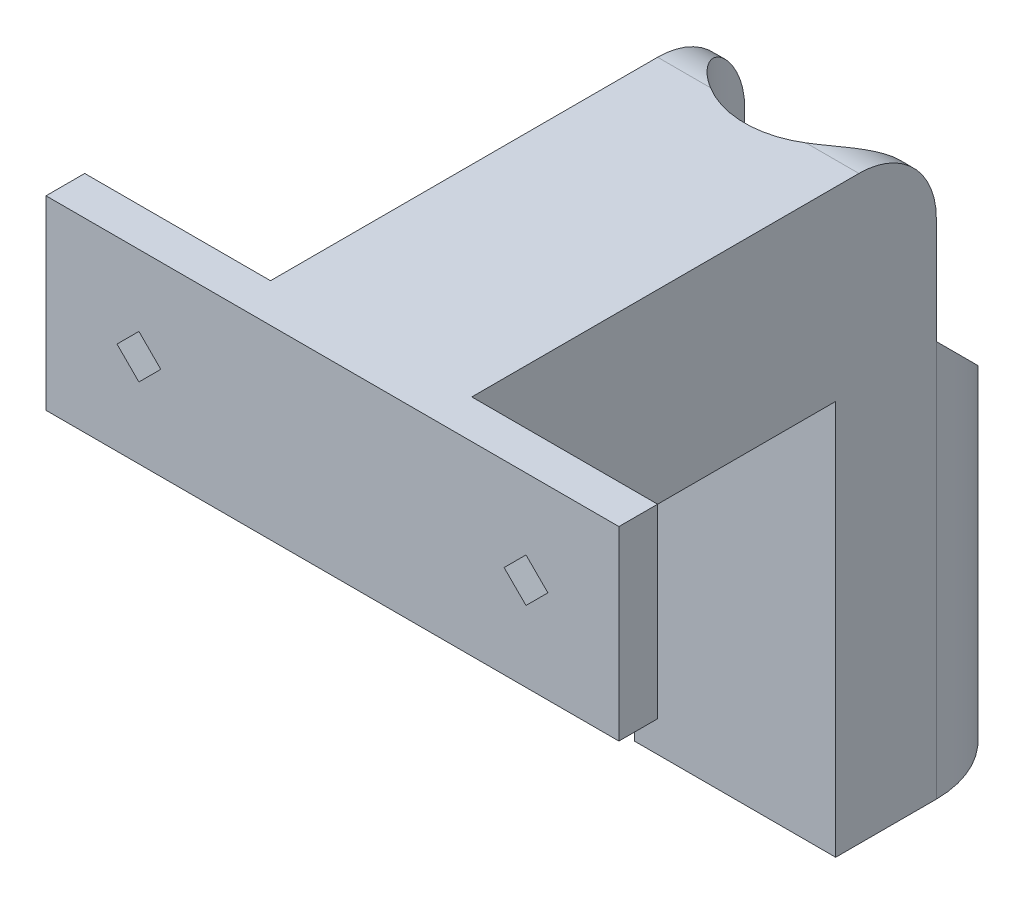
SolidWorks part; units mm, degrees
ref_plane "Front Plane" through (0, 0, 0) normal (0, 0, 1) x (1, 0, 0)
ref_plane "Top Plane" through (0, 0, 0) normal (0, 1, 0) x (1, 0, 0)
ref_plane "Right Plane" through (0, 0, 0) normal (1, 0, 0) x (0, 0, -1)
sketch "Sketch1" plane through (0, 0, 0) normal (0, 1, 0) x (1, 0, 0)
  circle A0 centre (0, 0) radius 11.25
  circle A1 centre (0, 0) radius 13
  dimension "D1" = 22.5
  dimension "D2" = 26
extrude "Boss-Extrude1" add sketch "Sketch1" along normal blind 1.2
sketch "Sketch2" plane through (0, 1.2, 0) normal (0, 1, 0) x (1, 0, 0)
  circle A0 centre (0, 0) radius 11.75
  circle A1 centre (0, 0) radius 13
  circle A2 centre (0, 0) radius 13 construction
  dimension "D1" = 23.5
extrude "Boss-Extrude2" add sketch "Sketch2" along normal blind 50
chamfer "Chamfer1" distance 0.5 angle 45 1 edges at (0, 1.2, 11.25)
sketch "Sketch3" plane through (0, 0, 0) normal (0, -1, 0) x (1, 0, 0)
  line L0 (-13, 0) -> (-13, 13)
  line L1 (-13, 13) -> (0, 13)
  line L2 (0, 13) -> (13, 13)
  line L3 (13, 13) -> (13, 0)
  line L4 (13, 0) -> (11.75, 0)
  line L5 (-13, 0) -> (-11.75, 0)
  circle A0 centre (0, 0) radius 13 construction
  circle A1 centre (0, 0) radius 11.75 construction
  arc A2 (11.75, 0) -> (-11.75, 0) centre (0, 0) ccw
  circle A3 centre (0, 0) radius 11.75 construction
  circle A4 centre (0, 0) radius 13 construction
extrude "Boss-Extrude3" add sketch "Sketch3" against normal blind 75
sketch "Sketch4" plane through (13, 0, 0) normal (1, 0, 0) x (0, 0, -1)
  line L1 (-13, 75) -> (-65, 75)
  line L2 (-13, 75) -> (-13, 51)
  line L3 (-13, 51) -> (-65, 51)
  line L4 (-65, 75) -> (-65, 51)
  dimension "D1" = 52
  dimension "D2" = 24
extrude "Boss-Extrude4" add sketch "Sketch4" against normal up to surface (26 mm away) up to face at (-13, 40.24, 5.2)
sketch "Sketch5" plane through (0, 0, 65) normal (0, 0, 1) x (1, 0, 0)
  line L0 (-13, 75) -> (-13, 51) construction
  line L1 (-13, 75) -> (-37, 75)
  line L2 (-13, 75) -> (-13, 51)
  line L3 (-13, 51) -> (-37, 51)
  line L4 (-37, 75) -> (-37, 51)
  line L5 (13, 51) -> (37, 51)
  line L6 (13, 51) -> (13, 75)
  line L7 (13, 75) -> (37, 75)
  line L8 (37, 51) -> (37, 75)
  line L9 (-13, 75) -> (13, 75) construction
  line L10 (-37, 75) -> (-13, 51) construction
  line L11 (-13, 75) -> (-37, 51) construction
  line L12 (13, 75) -> (37, 51) construction
  line L13 (37, 75) -> (13, 51) construction
  line L14 (-27.8284, 63) -> (-25, 65.8284)
  line L15 (-27.8284, 63) -> (-25, 60.1716)
  line L16 (-25, 65.8284) -> (-22.1716, 63)
  line L17 (-25, 60.1716) -> (-22.1716, 63)
  line L18 (-27.8284, 63) -> (-22.1716, 63) construction
  line L19 (-25, 65.8284) -> (-25, 60.1716) construction
  line L20 (22.1716, 63) -> (25, 65.8284)
  line L21 (22.1716, 63) -> (25, 60.1716)
  line L22 (25, 65.8284) -> (27.8284, 63)
  line L23 (25, 60.1716) -> (27.8284, 63)
  line L24 (22.1716, 63) -> (27.8284, 63) construction
  line L25 (25, 65.8284) -> (25, 60.1716) construction
  point P10 (-25, 63)
  point P15 (25, 63)
  point P16 (-25, 63)
  point P17 (25, 63)
  dimension "D1" = 24
  dimension "D2" = 24
  dimension "D3" = 4
  dimension "D4" = 4
  dimension "D5" = 4
  dimension "D6" = 4
extrude "Boss-Extrude5" add sketch "Sketch5" against normal blind 5
sketch "Sketch6" plane through (-13, 0, 0) normal (-1, 0, 0) x (0, 0, 1)
  line L0 (0, 51.2) -> (-13, 38.2)
  line L1 (-13, 51.2) -> (-13, 0) construction
  line L2 (-13, 38.2) -> (-13, 51.2)
  line L3 (-13, 51.2) -> (0, 51.2)
extrude "Cut-Extrude1" cut sketch "Sketch6" against normal through all
fillet "Fillet1" radius 10 2 edges at (12.375, 75, 0) (-12.375, 75, 0)
